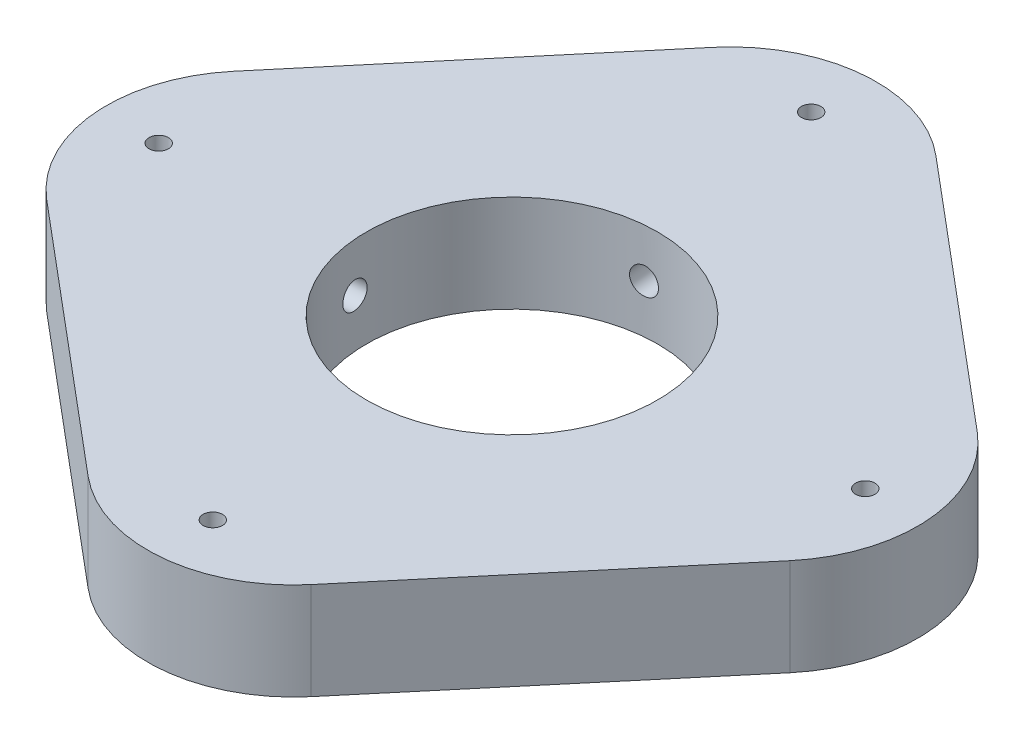
SolidWorks part; units mm, degrees
ref_plane "Front Plane" through (0, 0, 0) normal (0, 0, 1) x (1, 0, 0)
ref_plane "Top Plane" through (0, 0, 0) normal (0, 1, 0) x (1, 0, 0)
ref_plane "Right Plane" through (0, 0, 0) normal (1, 0, 0) x (0, 0, -1)
sketch "Sketch2" plane through (0, 0, 0) normal (0, 1, 0) x (1, 0, 0)
  line L0 (33.9016, 14.0205) -> (7.1139, 36.5465)
  line L1 (-14.0205, 34.72) -> (-36.5465, 7.9323)
  line L2 (-34.72, -13.2021) -> (-7.9323, -35.7281)
  line L3 (13.2021, -33.9016) -> (35.7281, -7.1139)
  circle A0 centre (-0.4092, 0.4092) radius 16.2
  arc A1 (35.7281, -7.1139) -> (33.9016, 14.0205) centre (24.2476, 2.5401) ccw
  arc A2 (7.1139, 36.5465) -> (-14.0205, 34.72) centre (-2.5401, 25.066) ccw
  arc A3 (-36.5465, 7.9323) -> (-34.72, -13.2021) centre (-25.066, -1.7217) ccw
  arc A4 (-7.9323, -35.7281) -> (13.2021, -33.9016) centre (1.7217, -24.2476) ccw
extrude "Boss-Extrude2" add sketch "Sketch2" along normal blind 10
sketch "Sketch3" plane through (0, 10, 0) normal (0, 1, 0) x (1, 0, 0)
  line L4 (-3.8316, 40.0103) -> (-3.1946, 34.0103) construction
  line L5 (-40.0103, -3.0132) -> (-34.0103, -2.3762) construction
  line L6 (39.1919, 3.8316) -> (33.1919, 3.1946) construction
  line L7 (3.0132, -39.1919) -> (2.3762, -33.1919) construction
  circle A0 centre (-0.4092, 0.4092) radius 16.2 construction
  circle A1 centre (-0.4092, 0.4092) radius 16.2
  arc A10 (-36.5465, 7.9323) -> (-34.72, -13.2021) centre (-25.066, -1.7217) ccw construction
  circle A11 centre (-34.0103, -2.3762) radius 1
  circle A12 centre (-3.1946, 34.0103) radius 1
  circle A13 centre (33.1919, 3.1946) radius 1
  circle A14 centre (2.3762, -33.1919) radius 1
  point P15 (-0.4092, 0.4092)
  dimension "D2" = 4
  dimension "D1" = 6
extrude "Cut-Extrude2" cut sketch "Sketch3" against normal blind 10
sketch "Sketch4" plane through (0, 10, 0) normal (0, 1, 0) x (1, 0, 0)
  circle A0 centre (-0.4092, 0.4092) radius 15
  circle A1 centre (-0.4092, 0.4092) radius 16.2 construction
  circle A2 centre (-0.4092, 0.4092) radius 16.2
  dimension "D1" = 30
extrude "Boss-Extrude3" add sketch "Sketch4" against normal up to surface (10 mm away) up to face at (-34.0103, 0, 3.3762)
ref_plane "Plane1" through (-0.3711, 0, 0.0321) normal (0.9963, 0, -0.0861) x (-0.0861, 0, -0.9963)
sketch "Sketch7" plane through (-0.3711, 0, 0.0321) normal (0.9963, 0, -0.0861) x (-0.0861, 0, -0.9963)
  line L0 (15.4429, 10) -> (-14.5571, 10) construction
  line L1 (15.4429, 10) -> (-14.5571, 10)
  line L2 (-14.5571, 0) -> (15.4429, 0) construction
  line L3 (-14.5571, 0) -> (15.4429, 0)
  line L4 (0.4429, 0) -> (0.4429, 10) construction
  circle A0 centre (0.4429, 5) radius 1.375
  dimension "D1" = 2.75
extrude "Cut-Extrude3" cut sketch "Sketch7" against normal blind 25 and the other way blind 25 contours L4 A0 | A0 L4 region at (-0.3589, 5, 0.1722) region at (-0.4594, 5, -0.9906)
ref_plane "Plane2" through (-0.0381, 0, -0.4413) normal (0.0861, 0, 0.9963) x (0.9963, 0, -0.0861)
sketch "Sketch8" plane through (-0.0381, 0, -0.4413) normal (0.0861, 0, 0.9963) x (0.9963, 0, -0.0861)
  line L0 (-15.3724, 0) -> (14.6276, 0) construction
  line L1 (14.6276, 10) -> (-15.3724, 10) construction
  line L2 (-15.3724, 0) -> (14.6276, 0)
  line L3 (14.6276, 10) -> (-15.3724, 10)
  line L4 (-0.3724, 10) -> (-0.3724, 0) construction
  circle A0 centre (-0.3724, 5) radius 1.375
  dimension "D1" = 2.75
extrude "Cut-Extrude4" cut sketch "Sketch8" against normal blind 25 and the other way blind 25 contours A0 L4 | L4 A0 region at (0.1722, 5, -0.4594) region at (-0.9906, 5, -0.3589)
